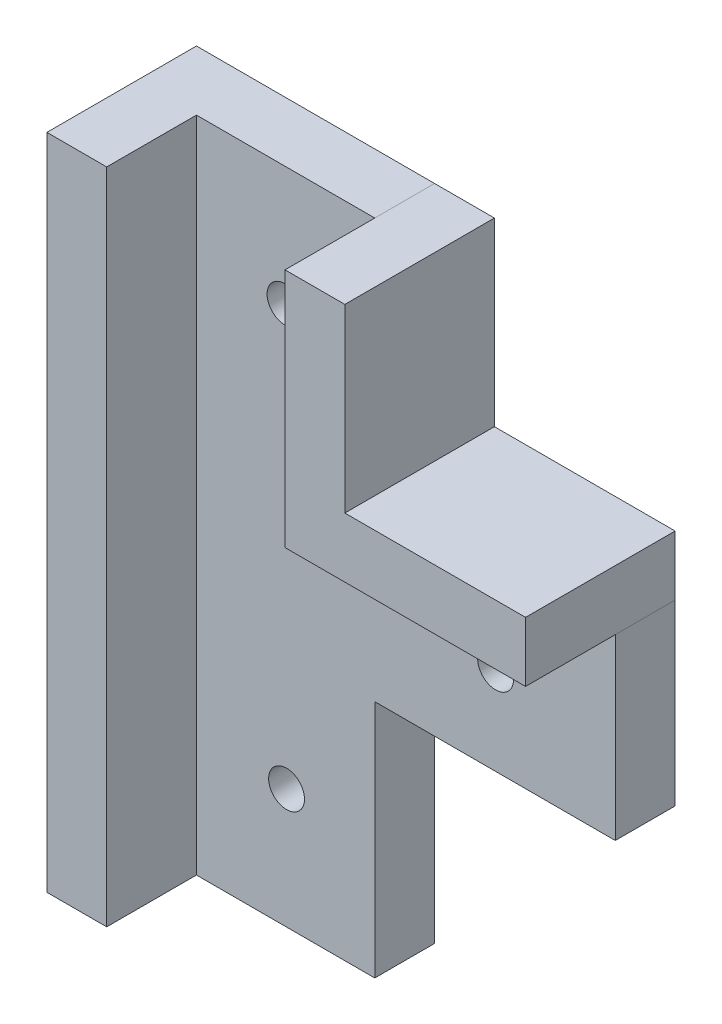
SolidWorks part; units mm, degrees
ref_plane "前视基准面" through (0, 0, 0) normal (0, 0, 1) x (1, 0, 0)
ref_plane "上视基准面" through (0, 0, 0) normal (0, 1, 0) x (1, 0, 0)
ref_plane "右视基准面" through (0, 0, 0) normal (1, 0, 0) x (0, 0, -1)
sketch "Sketch1" plane through (0, 0, 0) normal (0, 0, 1) x (1, 0, 0)
  line L0 (7.3701, -25.8068) -> (27.4701, -25.8068)
  line L3 (-7.5299, 9.1932) -> (7.3701, 9.1932)
  line L4 (-7.5299, 9.1932) -> (-7.5299, -25.8068)
  line L6 (7.3701, 9.1932) -> (7.3701, -10.9068)
  line L7 (27.4701, -25.8068) -> (27.4701, -10.9068)
  line L8 (27.4701, -10.9068) -> (7.3701, -10.9068)
  line L12 (-7.5299, -25.8068) -> (7.3701, -25.8068)
  dimension "D1" = 14.9
  dimension "D2" = 35
  dimension "D3" = 35
  dimension "D4" = 14.9
extrude "Boss-Extrude1" add sketch "Sketch1" along normal blind 5
sketch "Sketch2" plane through (0, 0, 0) normal (0, 0, -1) x (-1, 0, 0)
  line L0 (-7.3701, 9.1932) -> (-12.3701, 9.1932)
  line L1 (-12.3701, 9.1932) -> (-12.3701, -5.9068)
  line L2 (-12.3701, -5.9068) -> (-27.4701, -5.9068)
  line L3 (-27.4701, -10.9068) -> (-27.4701, -5.9068)
  line L4 (-27.4701, -10.9068) -> (-7.3701, -10.9068)
  line L5 (-7.3701, -10.9068) -> (-7.3701, 9.1932)
  dimension "D1" = 5
  dimension "D2" = 5
extrude "Boss-Extrude2" add sketch "Sketch2" against normal blind 12.5 separate body
sketch "Sketch3" plane through (0, 0, 0) normal (0, 0, -1) x (-1, 0, 0)
  line L0 (7.5299, 9.1932) -> (12.5299, 9.1932)
  line L2 (12.5299, -45.8068) -> (12.5299, 9.1932)
  line L3 (7.5299, -25.8068) -> (7.5299, 9.1932)
  line L5 (7.5299, -25.8068) -> (7.5299, -45.8068)
  line L6 (7.5299, -45.8068) -> (12.5299, -45.8068)
  dimension "D1" = 5
  dimension "D2" = 55
extrude "Boss-Extrude3" add sketch "Sketch3" against normal blind 12.5 separate body
sketch "Sketch4" plane through (0, 0, 0) normal (0, 0, -1) x (-1, 0, 0)
  line L0 (-27.4701, -10.9068) -> (-7.3701, -10.9068) construction
  line L1 (-27.4701, -25.8068) -> (-27.4701, -10.9068) construction
  line L2 (-7.3701, -10.9068) -> (-7.3701, 9.1932) construction
  line L3 (-7.3701, 9.1932) -> (7.5299, 9.1932) construction
  circle A0 centre (0.1299, -0.8068) radius 1.5
  circle A1 centre (-17.4701, -18.4068) radius 1.5
  dimension "D1" = 3
  dimension "D2" = 3
  dimension "D3" = 7.5
  dimension "D4" = 10
  dimension "D5" = 7.5
  dimension "D6" = 10
extrude "Cut-Extrude1" cut sketch "Sketch4" against normal through all
sketch "Sketch6" plane through (0, 0, 5) normal (0, 0, 1) x (1, 0, 0)
  line L0 (-7.5299, -25.8068) -> (-7.5299, -45.8068)
  line L1 (-7.5299, -25.8068) -> (27.4701, -25.8068) construction
  line L2 (-7.5299, -45.8068) -> (7.3701, -45.8068)
  line L3 (7.3701, -45.8068) -> (7.3701, -25.8068)
  line L4 (7.3701, -25.8068) -> (-7.5299, -25.8068)
  dimension "D1" = 14.9
  dimension "D2" = 20
extrude "Boss-Extrude4" add sketch "Sketch6" against normal blind 5
sketch "Sketch8" plane through (0, 0, 5) normal (0, 0, 1) x (1, 0, 0)
  line L0 (-7.5299, -45.8068) -> (7.3701, -45.8068) construction
  circle A0 centre (0, -35.8068) radius 1.5
  dimension "D1" = 3
  dimension "D2" = 10
extrude "Cut-Extrude2" cut sketch "Sketch8" against normal through all
